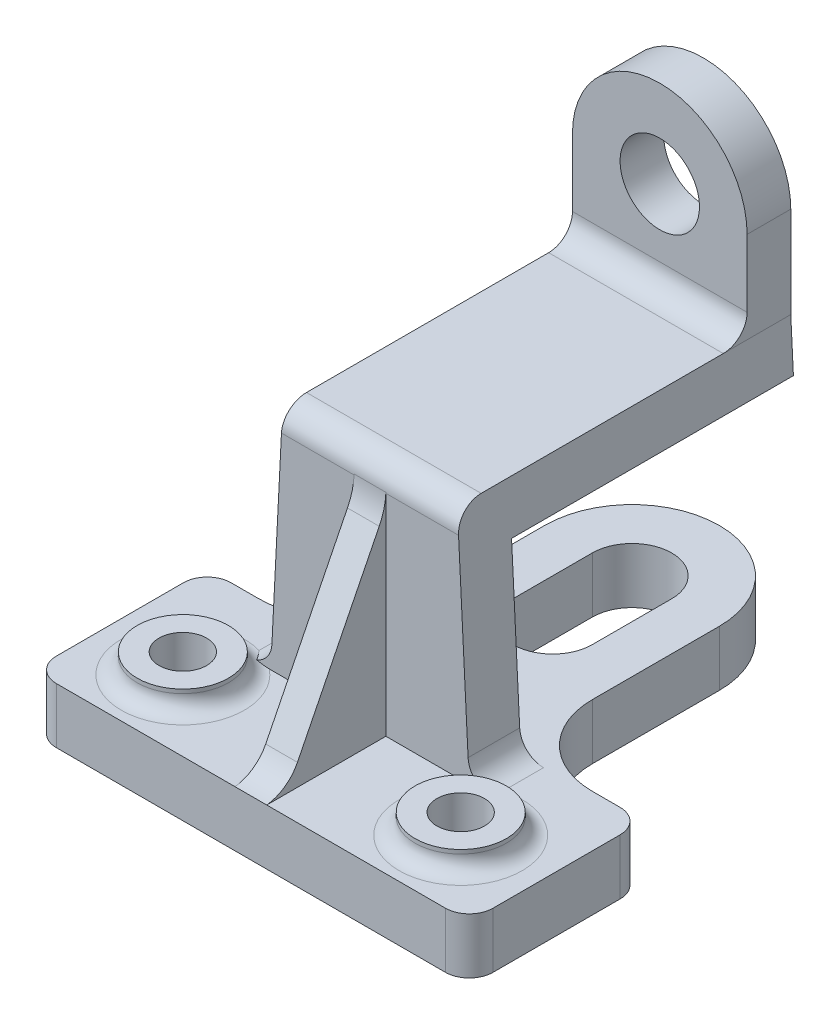
SolidWorks part; units mm, degrees
ref_plane "Piano frontale" through (0, 0, 0) normal (0, 0, 1) x (1, 0, 0)
ref_plane "Piano superiore" through (0, 0, 0) normal (0, 1, 0) x (1, 0, 0)
ref_plane "Piano destro" through (0, 0, 0) normal (1, 0, 0) x (0, 0, -1)
sketch "Schizzo1" plane through (0, 0, 0) normal (1, 0, 0) x (0, 0, -1)
  line L0 (0, 0) -> (-118, 0)
  line L1 (-118, 0) -> (-118, 14)
  line L2 (-118, 14) -> (-88, 14)
  line L3 (-88, 14) -> (-88, 73)
  line L4 (-88, 73) -> (-15, 73)
  line L5 (-15, 73) -> (-15, 118)
  line L6 (-15, 118) -> (-4, 118)
  line L7 (-4, 118) -> (-4, 60)
  line L8 (-4, 60) -> (-75, 60)
  line L9 (-75, 60) -> (-75, 14)
  line L10 (-75, 14) -> (0, 14)
  line L11 (0, 14) -> (0, 0)
  dimension "D1" = 73
  dimension "D2" = 11
  dimension "D3" = 13
  dimension "D4" = 13
  dimension "D5" = 14
  dimension "D6" = 60
  dimension "D7" = 118
  dimension "D8" = 30
  dimension "D9" = 118
  dimension "D10" = 114
extrude "Estrusione-Estrusione2" add sketch "Schizzo1" against normal blind 55
sketch "Schizzo2" plane through (-55, 0, 0) normal (-1, 0, 0) x (0, 0, 1)
  line L0 (88, 64) -> (113, 14)
  line L1 (88, 73) -> (88, 14) construction
  line L2 (88, 14) -> (118, 14) construction
  dimension "D1" = 25
  dimension "D2" = 50
rib "Nervatura1" sketch "Schizzo2" sketch "Schizzo2" thickness 4 extrusion direction parallel to sketch draft on no parameters "D1"=4
sketch "Schizzo3" plane through (0, 0, 0) normal (1, 0, 0) x (0, 0, -1)
  line L1 (-4, 118) -> (-88, 118)
  line L2 (-4, 118) -> (-4, 14)
  line L3 (-4, 14) -> (-88, 14)
  line L4 (-88, 118) -> (-88, 14)
extrude "Taglio-Estrusione1" cut sketch "Schizzo3" against normal blind 30
sketch "Schizzo4" plane through (0, 0, 0) normal (1, 0, 0) x (0, 0, -1)
  line L0 (-118, 0) -> (0, 0) construction
  line L1 (0, 14) -> (-74, 14)
  line L2 (0, 14) -> (0, 0)
  line L3 (0, 0) -> (-74, 0)
  line L4 (-74, 14) -> (-74, 0)
  dimension "D1" = 74
extrude "Taglio-Estrusione2" cut sketch "Schizzo4" against normal blind 33
mirror "Specchia2" about plane through (-55, 0, 0) normal (-1, 0, 0) of "Estrusione-Estrusione2", "Nervatura1", "Taglio-Estrusione1", "Taglio-Estrusione2"
fillet "Raccordo1" 2 edges at (-33, 7, 0) (-77, 7, 0) type full round first side face at (-33, 7, 37) second side face at (-77, 7, 37) middle face at (-55, 7, 0)
fillet "Raccordo3" radius 20 2 edges at (-77, 7, 74) (-33, 7, 74)
fillet "Raccordo4" radius 6 4 edges at (-110, 7, 74) (-110, 7, 118) (0, 7, 74) (0, 7, 118)
sketch "Schizzo6" plane through (0, 0, 88) normal (0, 0, 1) x (1, 0, 0)
  line L0 (-55, 73) -> (-55, 36.5978) construction
  line L1 (-80, 73) -> (-30, 73) construction
  line L2 (-77, 73) -> (-33, 73) construction
  line L3 (-33, 73) -> (-30, 14)
  line L4 (-30, 14) -> (-30, 73)
  line L5 (-30, 73) -> (-33, 73)
  line L6 (-80, 14) -> (-80, 73)
  line L7 (-77, 73) -> (-80, 14)
  line L8 (-80, 73) -> (-77, 73)
  dimension "D1" = 44
extrude "Taglio-Estrusione3" cut sketch "Schizzo6" against normal through all
sketch "Schizzo7" plane through (0, 0, 15) normal (0, 0, 1) x (1, 0, 0)
  line L0 (-55, 145.6565) -> (-55, 90.3435) construction
  line L2 (-77, 73) -> (-33, 73) construction
  line L3 (-30, 118) -> (-33, 118)
  line L4 (-30, 118) -> (-30, 73)
  line L5 (-30, 73) -> (-33, 73)
  line L6 (-33, 118) -> (-33, 73)
  line L7 (-80, 73) -> (-77, 73)
  line L8 (-80, 118) -> (-77, 118)
  line L9 (-80, 118) -> (-80, 73)
  line L10 (-77, 118) -> (-77, 73)
  point P3 (-55, 118)
  dimension "D1" = 44
extrude "Taglio-Estrusione4" cut sketch "Schizzo7" against normal through all
fillet "Raccordo11" 2 edges at (-33, 118, 9.5) (-77, 118, 9.5) type full round first side face at (-33, 95.5, 9.5) second side face at (-77, 95.5, 9.5) middle face at (-55, 118, 9.5)
fillet "Raccordo12" radius 6 2 edges at (-55, 73, 15) (-55, 73, 88)
fillet "Raccordo13" radius 16 1 edges at (-55, 64, 88)
fillet "Raccordo15" radius 10 1 edges at (-55, 14, 113)
sketch "Schizzo8" plane through (0, 0, 15) normal (0, 0, 1) x (1, 0, 0)
  line L0 (-33, 96) -> (-33, 79) construction
  circle A0 centre (-55, 96) radius 10
  arc A1 (-33, 96) -> (-77, 96) centre (-55, 96) ccw construction
  dimension "D3" = 20
  dimension "D1" = 22
  dimension "D2" = 0
extrude "Taglio-Estrusione5" cut sketch "Schizzo8" against normal through all
sketch "Schizzo9" plane through (0, 14, 0) normal (0, 1, 0) x (1, 0, 0)
  line L0 (-55, -118) -> (-55, 20.7041) construction
  line L1 (-59, -118) -> (-51, -118) construction
  circle A0 centre (-90, -100.1493) radius 11.5
  circle A1 centre (-20, -100.1493) radius 11.5
  dimension "D3" = 23
  dimension "D1" = 70
  dimension "D2" = 35
extrude "Estrusione-Estrusione3" add sketch "Schizzo9" along normal blind 5
sketch "Schizzo10" plane through (0, 19, 0) normal (0, 1, 0) x (1, 0, 0)
  circle A0 centre (-90, -100.1493) radius 6
  circle A1 centre (-20, -100.1493) radius 6
  circle A2 centre (-90, -100.1493) radius 11.5 construction
  circle A3 centre (-20, -100.1493) radius 11.5 construction
  dimension "D1" = 12
extrude "Taglio-Estrusione6" cut sketch "Schizzo10" against normal through all
sketch "Schizzo11" plane through (0, 0, 0) normal (0, -1, 0) x (1, 0, 0)
  line L0 (-55, 0) -> (-55, 118) construction
  line L1 (-104, 118) -> (-6, 118) construction
  line L2 (-65, 22) -> (-65, 42)
  line L3 (-55, 32) -> (-108.3828, 32) construction
  line L4 (-45, 22) -> (-45, 42)
  arc A0 (-77, 22) -> (-33, 22) centre (-55, 22) ccw construction
  arc A1 (-65, 22) -> (-45, 22) centre (-55, 22) ccw
  arc A2 (-65, 42) -> (-45, 42) centre (-55, 42) cw
  point P14 (-65, 32)
  dimension "D1" = 10
  dimension "D2" = 10
  dimension "D3" = 22
extrude "Taglio-Estrusione7" cut sketch "Schizzo11" against normal up to next
fillet "Raccordo17" radius 4 2 edges at (-90, 14, 111.6493) (-20, 14, 111.6493)
fillet "Raccordo18" radius 6 2 edges at (-80, 14, 81.5) (-30, 14, 81.5)
